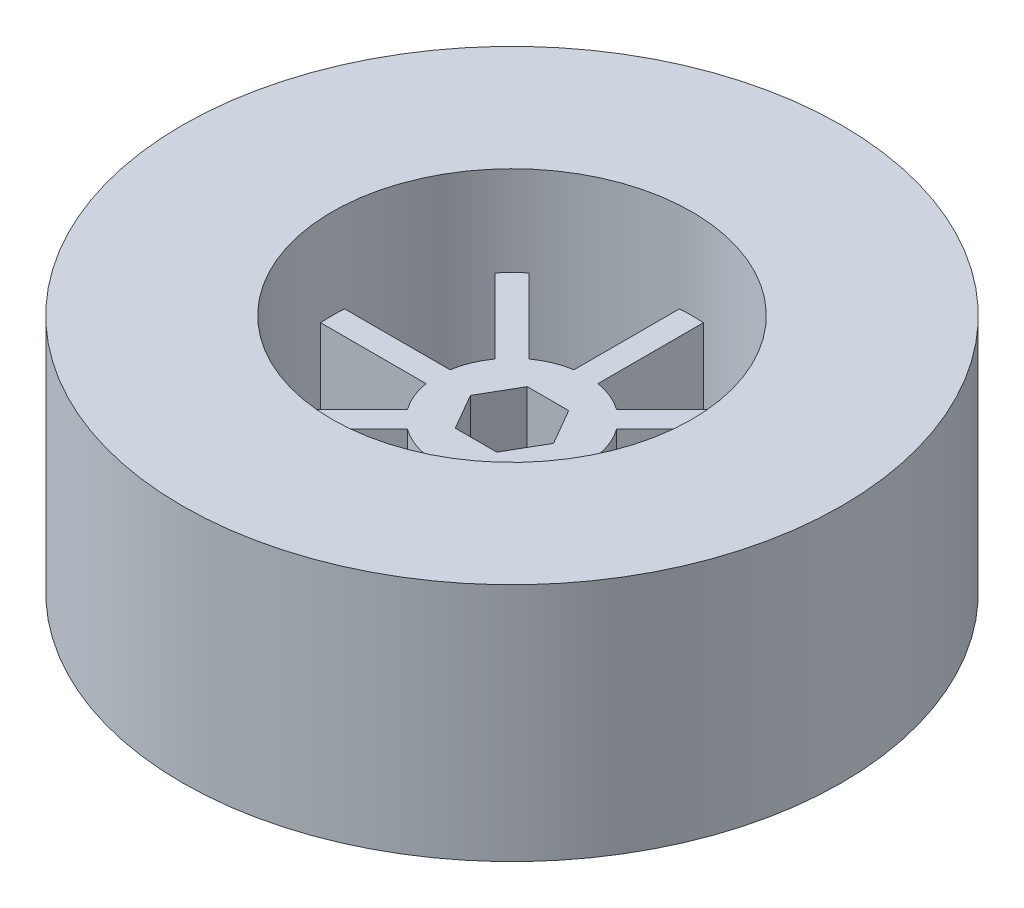
SolidWorks part; units mm, degrees
ref_plane "Front Plane" through (0, 0, 0) normal (0, 0, 1) x (1, 0, 0)
ref_plane "Top Plane" through (0, 0, 0) normal (0, 1, 0) x (1, 0, 0)
ref_plane "Right Plane" through (0, 0, 0) normal (1, 0, 0) x (0, 0, -1)
sketch "Sketch2" plane through (0, 0, 0) normal (0, 1, 0) x (1, 0, 0)
  line L0 (0, 12.5) -> (0, 30) construction
  line L7 (2, 29.9333) -> (2, 12.339)
  line L8 (-2, 29.9333) -> (-2, 12.339)
  line L9 (19.7518, 22.5802) -> (7.3108, 10.1392)
  line L10 (22.5802, 19.7518) -> (10.1392, 7.3108)
  line L11 (8.8388, 8.8388) -> (21.2132, 21.2132) construction
  line L12 (29.9333, 2) -> (12.339, 2)
  line L13 (29.9333, -2) -> (12.339, -2)
  line L14 (12.5, 0) -> (30, 0) construction
  line L15 (22.5802, -19.7518) -> (10.1392, -7.3108)
  line L16 (19.7518, -22.5802) -> (7.3108, -10.1392)
  line L17 (8.8388, -8.8388) -> (21.2132, -21.2132) construction
  line L18 (2, -29.9333) -> (2, -12.339)
  line L19 (-2, -29.9333) -> (-2, -12.339)
  line L20 (0, -12.5) -> (0, -30) construction
  line L21 (-19.7518, -22.5802) -> (-7.3108, -10.1392)
  line L22 (-22.5802, -19.7518) -> (-10.1392, -7.3108)
  line L23 (-8.8388, -8.8388) -> (-21.2132, -21.2132) construction
  line L24 (-29.9333, -2) -> (-12.339, -2)
  line L25 (-29.9333, 2) -> (-12.339, 2)
  line L26 (-12.5, 0) -> (-30, 0) construction
  line L27 (-22.5802, 19.7518) -> (-10.1392, 7.3108)
  line L28 (-19.7518, 22.5802) -> (-7.3108, 10.1392)
  line L29 (-8.8388, 8.8388) -> (-21.2132, 21.2132) construction
  circle A0 centre (0, 0) radius 55
  arc A1 (-22.5802, 19.7518) -> (-29.9333, 2) centre (0, 0) ccw
  arc A2 (-2, 12.339) -> (-7.3108, 10.1392) centre (0, 0) ccw
  arc A3 (-2, 29.9333) -> (-19.7518, 22.5802) centre (0, 0) ccw
  arc A4 (-10.1392, 7.3108) -> (-12.339, 2) centre (0, 0) ccw
  arc A5 (-12.339, -2) -> (-10.1392, -7.3108) centre (0, 0) ccw
  arc A6 (-29.9333, -2) -> (-22.5802, -19.7518) centre (0, 0) ccw
  arc A7 (-7.3108, -10.1392) -> (-2, -12.339) centre (0, 0) ccw
  arc A8 (-19.7518, -22.5802) -> (-2, -29.9333) centre (0, 0) ccw
  arc A9 (2, -12.339) -> (7.3108, -10.1392) centre (0, 0) ccw
  arc A10 (10.1392, -7.3108) -> (12.339, -2) centre (0, 0) ccw
  arc A11 (12.339, 2) -> (10.1392, 7.3108) centre (0, 0) ccw
  arc A12 (7.3108, 10.1392) -> (2, 12.339) centre (0, 0) ccw
  arc A13 (2, -29.9333) -> (19.7518, -22.5802) centre (0, 0) ccw
  arc A14 (22.5802, -19.7518) -> (29.9333, -2) centre (0, 0) ccw
  arc A15 (29.9333, 2) -> (22.5802, 19.7518) centre (0, 0) ccw
  arc A16 (19.7518, 22.5802) -> (2, 29.9333) centre (0, 0) ccw
  point P54 (0, 0)
  dimension "D1" = 110
  dimension "D2" = 2
  dimension "D3" = 25
  dimension "D4" = 60
  dimension "D5" = 2
  dimension "D6" = 8
extrude "Wheel_Extrude" add sketch "Sketch2" along normal blind 40
sketch "Sketch4" plane through (0, 40, 0) normal (0, 1, 0) x (1, 0, 0)
  line L1 (6.9282, 0) -> (3.4641, 6)
  line L2 (3.4641, 6) -> (-3.4641, 6)
  line L3 (-3.4641, 6) -> (-6.9282, 0)
  line L4 (-6.9282, 0) -> (-3.4641, -6)
  line L5 (-3.4641, -6) -> (3.4641, -6)
  line L6 (3.4641, -6) -> (6.9282, 0)
  circle A0 centre (0, 0) radius 30
  circle A1 centre (0, 0) radius 6 construction
  dimension "D1" = 12
  dimension "D2" = 60
extrude "Wheel_Inset" cut sketch "Sketch4" against normal blind 15 contours A0
extrude "Hub_Inset" cut sketch "Sketch4<4>" against normal blind 25 contours L2 L3 L4 L5 L6 L1
sketch "Sketch4<4>" plane through (0, 40, 0) normal (0, 1, 0) x (1, 0, 0) same geometry as "Sketch4"
ref_axis "CentreAxis" through (0, 0, 0) along (0, 1, 0)
sketch "Sketch7" plane through (0, 0, 0) normal (1, 0, 0) x (0, 0, -1)
  line L0 (0, 0) -> (0, 40) construction
  line L1 (30, 40) -> (-30, 40) construction
equation "\"Wheel_Inset\"= \"Hub_Inset\" - \"Hex_Length\""
equation "\"Hub_Inset\"= 25mm"
equation "\"Hex_Length\"= 10mm"
equation "\"D1@Wheel_Inset\"= \"Wheel_Inset\""
equation "\"D1@Hub_Inset\"=\"Hub_Inset\""
